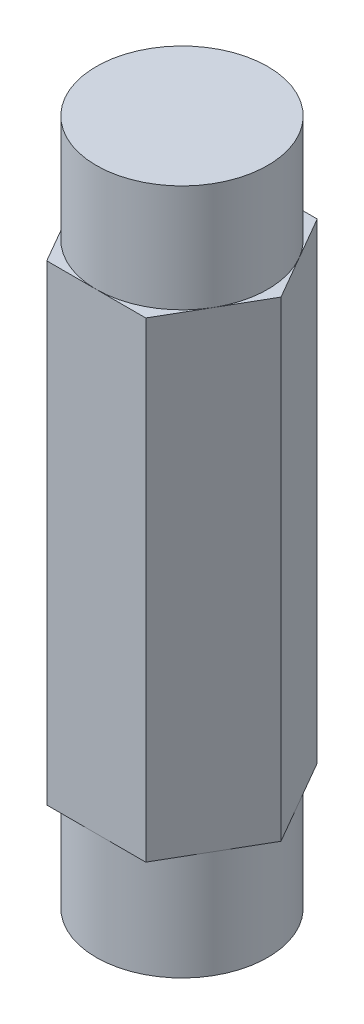
SolidWorks part; units mm, degrees
ref_plane "Front Plane" through (0, 0, 0) normal (0, 0, 1) x (1, 0, 0)
ref_plane "Top Plane" through (0, 0, 0) normal (0, 1, 0) x (1, 0, 0)
ref_plane "Right Plane" through (0, 0, 0) normal (1, 0, 0) x (0, 0, -1)
sketch "Sketch1" plane through (0, 0, 0) normal (0, 1, 0) x (1, 0, 0)
  line L1 (3.6662, -6.35) -> (7.3323, 0)
  line L2 (7.3323, 0) -> (3.6662, 6.35)
  line L3 (3.6662, 6.35) -> (-3.6662, 6.35)
  line L4 (-3.6662, 6.35) -> (-7.3323, 0)
  line L5 (-7.3323, 0) -> (-3.6662, -6.35)
  line L6 (-3.6662, -6.35) -> (3.6662, -6.35)
  circle A0 centre (0, 0) radius 6.35 construction
  dimension "D1" = 12.7
extrude "Boss-Extrude1" add sketch "Sketch1" along normal mid plane 50.8102 contours L1 L2 L3 L4 L5 L6
sketch "Sketch2" plane through (0, 25.4051, 0) normal (0, 1, 0) x (1, 0, 0)
  circle A0 centre (0, 0) radius 6.35
  dimension "D1" = 12.7
extrude "Cut-Extrude1" cut sketch "Sketch2" against normal blind 7.9502 flip side to cut
mirror "Mirror1" about plane through (0, 0, 0) normal (0, 1, 0) of "Cut-Extrude1"
equation "\"D1@Boss-Extrude1\"=1.9954+0.005"
